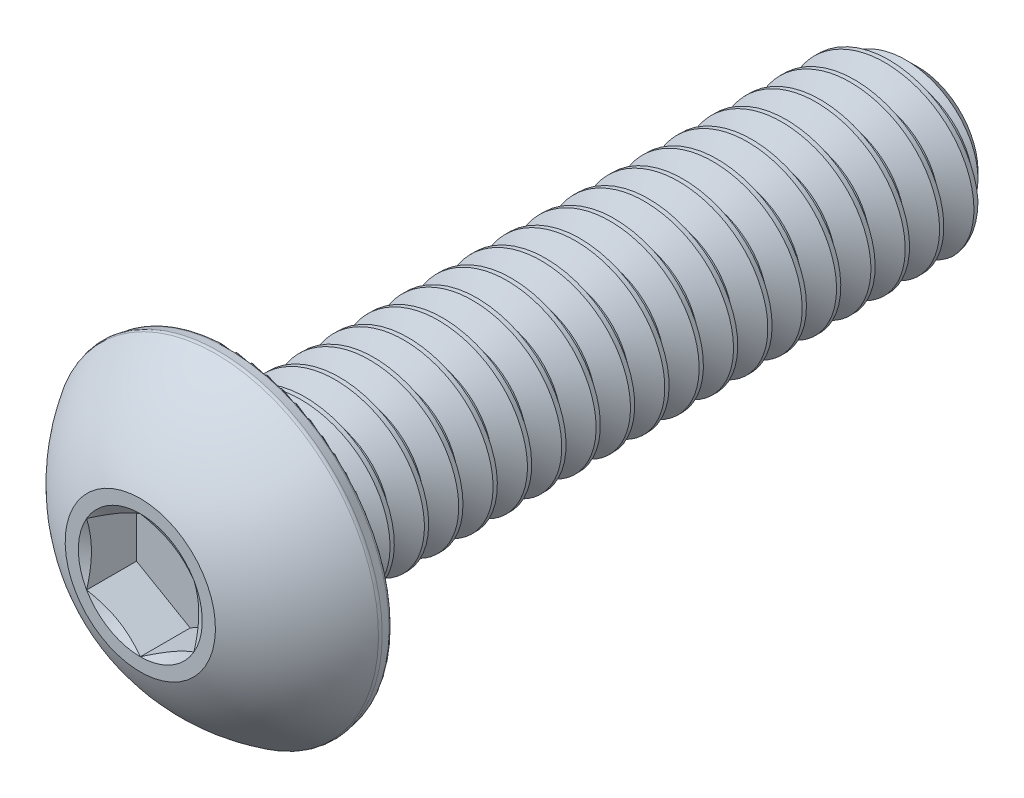
SolidWorks part; units mm, degrees
ref_plane "Front Plane" through (0, 0, 0) normal (0, 0, 1) x (1, 0, 0)
ref_plane "Top Plane" through (0, 0, 0) normal (0, 1, 0) x (1, 0, 0)
ref_plane "Right Plane" through (0, 0, 0) normal (1, 0, 0) x (0, 0, -1)
sketch "Sketch1" plane through (0, 0, 0) normal (1, 0, 0) x (0, 0, -1)
  line L0 (-7.1882, 0) -> (7.1882, 0) construction
  line L1 (-7.1882, 0) -> (-7.1882, 3.0226)
  line L2 (-7.1882, 3.0226) -> (-5.5118, 3.0226)
  line L3 (-5.5118, 3.0226) -> (-5.5118, 1.5875)
  line L4 (-5.5118, 1.5875) -> (7.1882, 1.5875)
  line L5 (7.1882, 1.5875) -> (7.1882, 0)
  point P2 (0, 0)
  point P4 (6.5532, 0)
  point P9 (6.2357, 1.5875)
  point P10 (6.2357, -1.5875)
  point P11 (7.1882, -1.5875)
  point P15 (-6.2662, 0)
  dimension "Head Height" = 1.6764
  dimension "Head Diameter" = 6.0452
  dimension "Length" = 12.7
  dimension "Screw Size Decimal Equivalent" = 3.175
  dimension "Thread Pitch" = 0.635
  dimension "D1" = 0.9525
  dimension "D2" = 0.922
sketch "Sketch2" plane through (0, 0, 0) normal (0, 0, 1) x (1, 0, 0)
  line L0 (0, 1.5875) -> (0, 0) construction
  line L1 (0, 1.1457) -> (-0.9922, 0.5728)
  line L2 (-0.9922, 0.5728) -> (-0.9922, -0.5728)
  line L3 (-0.9922, -0.5728) -> (0, -1.1457)
  line L4 (0, -1.1457) -> (0.9922, -0.5728)
  line L5 (0.9922, -0.5728) -> (0.9922, 0.5728)
  line L6 (0.9922, 0.5728) -> (0, 1.1457)
  circle A0 centre (0, 0) radius 0.9922 construction
  circle A1 centre (0, 0) radius 1.3891
  point P10 (0, 1.3891)
  dimension "D1" = 2.7781
  dimension "Drive Size" = 1.9844
sketch "Sketch3" plane through (0, 0, 0) normal (1, 0, 0) x (0, 0, -1)
  line L0 (-7.1882, 0) -> (-7.1882, 1.3891)
  line L1 (-7.1882, 0) -> (-7.1882, 3.0226) construction
  line L2 (-7.1882, 3.0226) -> (-5.5118, 3.0226) construction
  line L3 (-5.7633, 3.0226) -> (-5.5118, 2.9783)
  line L4 (-5.5118, 3.0226) -> (-5.5118, 1.5875) construction
  line L5 (-5.5118, 2.9783) -> (-5.5118, 1.5875)
  line L6 (-7.1882, 0) -> (7.1882, 0) construction
  line L7 (-7.1882, 0) -> (7.1882, 0)
  line L8 (7.1882, 0) -> (7.1882, 1.1113)
  line L9 (7.1882, 1.5875) -> (7.1882, 0) construction
  line L10 (7.1882, 1.1113) -> (6.7119, 1.5875)
  line L11 (-5.5118, 1.5875) -> (7.1882, 1.5875) construction
  line L12 (6.7119, 1.5875) -> (-5.5118, 1.5875)
  arc A0 (-7.1882, 1.3891) -> (-5.7633, 3.0226) centre (-3.947, 0) cw
  dimension "D1" = 0.2515
  dimension "D2" = 10
  dimension "D3" = 45
  dimension "D4" = 0.4763
revolve "Revolve1" add sketch "Sketch3" angle 360 about L7
sketch "Sketch4" plane through (0, 0, 7.1882) normal (0, 0, 1) x (1, 0, 0)
  line L0 (-0.9922, -0.5728) -> (0, -1.1457) construction
  line L1 (-0.9922, 0.5728) -> (-0.9922, -0.5728) construction
  line L2 (0, 1.1457) -> (-0.9922, 0.5728) construction
  line L3 (0.9922, 0.5728) -> (0, 1.1457) construction
  line L4 (0.9922, -0.5728) -> (0.9922, 0.5728) construction
  line L5 (0, -1.1457) -> (0.9922, -0.5728) construction
  line L6 (-0.9922, -0.5728) -> (0, -1.1457)
  line L7 (-0.9922, 0.5728) -> (-0.9922, -0.5728)
  line L8 (0, 1.1457) -> (-0.9922, 0.5728)
  line L9 (0.9922, 0.5728) -> (0, 1.1457)
  line L10 (0.9922, -0.5728) -> (0.9922, 0.5728)
  line L11 (0, -1.1457) -> (0.9922, -0.5728)
extrude "Cut-Extrude1" cut sketch "Sketch4" against normal up to vertex (0.922 mm away) up to point (0, 0, 6.2662)
sketch "Sketch5" plane through (0, 0, 7.1882) normal (0, 0, 1) x (1, 0, 0)
  circle A0 centre (0, 0) radius 1.1457
extrude "Cut-Extrude2" cut sketch "Sketch5" against normal up to vertex (0.922 mm away) draft 60 up to point (0, 0, 6.2662)
fillet "Fillet1" radius 0.0838 2 edges at (3.0226, 0, 5.7633) (2.9783, 0, 5.5118)
split "Split1" bodies to split 106 resulting bodies 107 108 split by face at (2.9079, 0, 5.5118)
sketch "Sketch6" plane through (0, 0, -7.1882) normal (0, 0, -1) x (-1, 0, 0)
  circle A0 centre (0, 0) radius 1.5875 construction
  circle A1 centre (0, 0) radius 1.5875
curve "Helix/Spiral1" pitch 0.635 height 13.335 radius 1.5875 centre (0, 0, -7.1882) axis (0, 0, 1) start towards (0, 1, 0)
sketch "Sketch7" plane through (0, 0, 0) normal (1, 0, 0) x (0, 0, -1)
  line L0 (7.1485, 1.6562) -> (7.466, 1.1063) construction
  line L1 (7.466, 1.1063) -> (7.7835, 1.6562) construction
  line L2 (7.7835, 1.6562) -> (7.1485, 1.6562) construction
  line L3 (7.1684, 1.6219) -> (7.7637, 1.6219)
  line L4 (7.7637, 1.6219) -> (7.5057, 1.1751)
  line L5 (7.5057, 1.1751) -> (7.4263, 1.1751)
  line L6 (7.4263, 1.1751) -> (7.1684, 1.6219)
  line L7 (7.466, 1.1751) -> (7.466, 1.1063) construction
  line L8 (7.1882, 1.5875) -> (7.7438, 1.5875) construction
  line L9 (7.466, 1.6562) -> (7.466, 1.5875) construction
  point P12 (7.466, 1.6219)
  dimension "D1" = 0.635
  dimension "D2" = 0.0794
sweep "Cut-Sweep1" cut profiles "Sketch7" path "Helix/Spiral1" align with end faces yes
sketch "Sketch8" plane through (0, 0, 5.5118) normal (0, 0, -1) x (-1, 0, 0)
  circle A0 centre (0, 0) radius 1.6562
extrude "Boss-Extrude1" add sketch "Sketch8" along normal up to vertex (11.7475 mm away) draft 45 up to point (0, 1.5875, -6.2357)
equation "\"D1@Sketch1\"=\"Thread Pitch@Sketch1\"*1.5"
equation "\"D2@Sketch1\"=0.55*\"Head Height@Sketch1\""
equation "\"D1@Sketch2\"=\"Drive Size@Sketch2\"*1.4"
equation "\"D1@Sketch3\"=0.15*\"Head Height@Sketch1\""
equation "\"D4@Sketch3\"=0.75*\"Thread Pitch@Sketch1\""
equation "\"D1@Fillet1\"=.05*\"Head Height@Sketch1\""
equation "\"D4@Helix/Spiral1\"=\"Thread Pitch@Sketch1\""
equation "\"D3@Helix/Spiral1\"=\"Length@Sketch1\"+\"Thread Pitch@Sketch1\""
equation "\"D2@Sketch7\"=\"D1@Sketch7\"/8"
equation "\"D1@Sketch7\"=\"Thread Pitch@Sketch1\""
